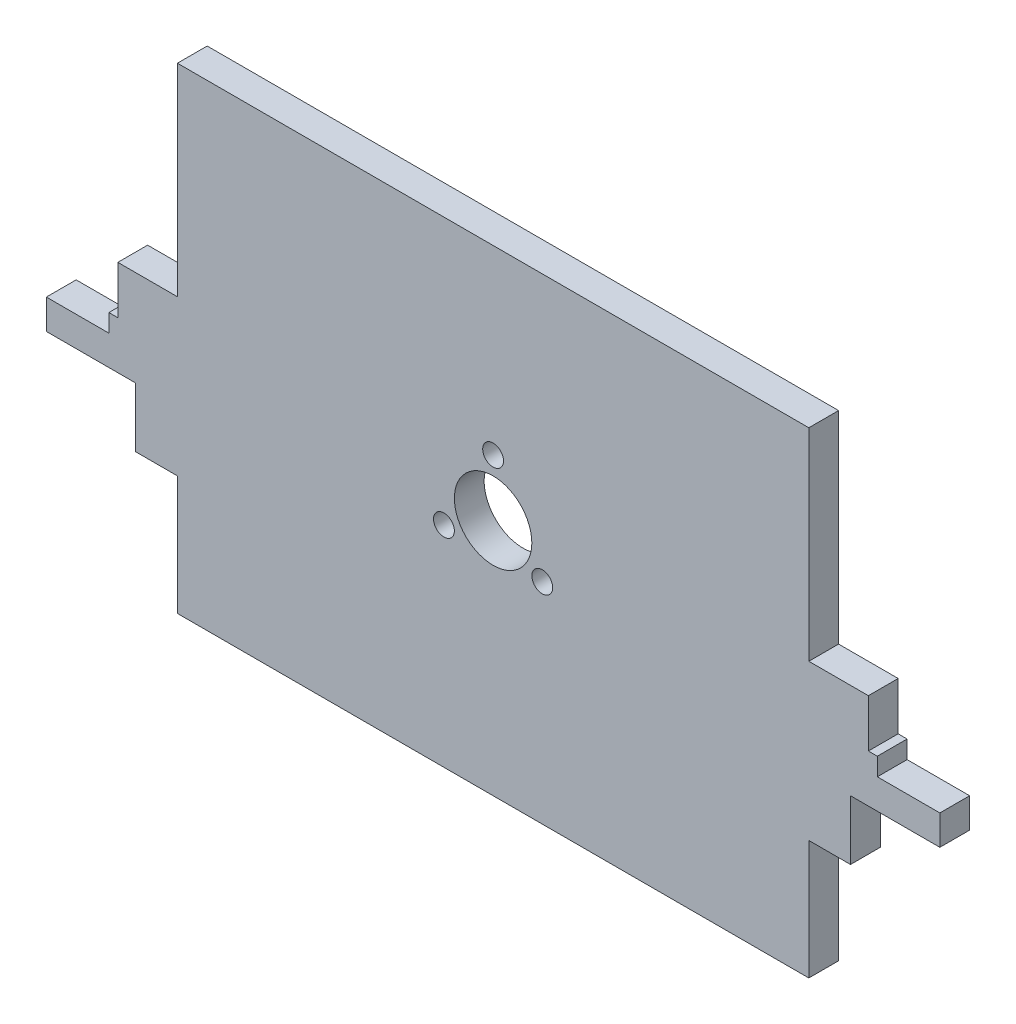
SolidWorks part; units mm, degrees
ref_plane "前视基准面" through (0, 0, 0) normal (0, 0, 1) x (1, 0, 0)
ref_plane "上视基准面" through (0, 0, 0) normal (0, 1, 0) x (1, 0, 0)
ref_plane "右视基准面" through (0, 0, 0) normal (1, 0, 0) x (0, 0, -1)
other "Configuration Table"
sketch "草图1" plane through (0, 0, 0) normal (0, 0, 1) x (1, 0, 0)
  line L1 (60, -45) -> (-60, -45)
  line L2 (60, -45) -> (60, 45)
  line L3 (60, 45) -> (-60, 45)
  line L4 (-60, -45) -> (-60, 45)
  line L5 (60, -45) -> (-60, 45) construction
  line L6 (60, 45) -> (-60, -45) construction
  point P0 (0, 0)
  dimension "D1" = 120
  dimension "D2" = 90
extrude "凸台-拉伸1" add sketch "草图1" along normal blind 5
sketch "草图5" plane through (0, 0, 0) normal (0, 0, -1) x (-1, 0, 0)
  line L0 (60, 45) -> (60, -45) construction
  line L1 (-60, -45) -> (60, -45)
  line L2 (-60, -45) -> (-60, -35)
  line L3 (-60, -35) -> (60, -35)
  line L4 (60, -45) -> (60, -35)
  dimension "D1" = 10
extrude "切除-拉伸3" cut sketch "草图5" against normal blind 10
sketch "草图8" plane through (60, 0, 0) normal (1, 0, 0) x (0, 0, -1)
  line L0 (0, 0.0974) -> (0, -5.0026)
  line L1 (0, -35) -> (0, 45) construction
  line L2 (-50.9779, 0.0974) -> (47.0221, 0.0974) construction
  line L3 (47.0221, -5.0026) -> (-50.9779, -5.0026) construction
  line L4 (0, -5.0026) -> (-5, -5.0026)
  line L5 (-5, -35) -> (-5, 45) construction
  line L6 (-5, -5.0026) -> (-5, 0.0974)
  line L7 (-5, 0.0974) -> (0, 0.0974)
  line L9 (-4.95, -5.0026) -> (-0.05, -5.0026)
  line L10 (-4.95, -5.0026) -> (-4.95, 0.0974)
  line L11 (-4.95, 0.0974) -> (-0.05, 0.0974)
  line L12 (-0.05, -5.0026) -> (-0.05, 0.0974)
  line L13 (-4.95, -5.0026) -> (-0.05, 0.0974) construction
  line L14 (-4.95, 0.0974) -> (-0.05, -5.0026) construction
  point P8 (-2.5, -2.4526)
  dimension "D1" = 0.05
  dimension "D2" = 0.05
  dimension "D3" = 0
  dimension "D4" = 0
sketch "草图10" plane through (60, 0, 0) normal (1, 0, 0) x (0, 0, -1)
  line L0 (-5, -35) -> (-5, 45) construction
  line L1 (0, 0) -> (-5, 0)
  line L2 (-5, 0) -> (-5, -5.0026)
  line L3 (-5, -5.0026) -> (0, -5.0026)
  line L4 (0, -35) -> (0, 45) construction
  line L5 (0, -5.0026) -> (0, 0)
extrude "凸台-拉伸3" add sketch "草图10" along normal blind 15
sketch "草图11" plane through (0, 0, 0) normal (0, 0, -1) x (-1, 0, 0)
  line L0 (0, 45) -> (0, -35) construction
  line L1 (-60, 45) -> (60, 45) construction
  line L2 (60, -35) -> (-60, -35) construction
sketch "草图12" plane through (-60, 0, 0) normal (-1, 0, 0) x (0, 0, 1)
  line L4 (0, 45) -> (0, -35)
  line L5 (0, -35) -> (5, -35)
  line L6 (5, -35) -> (5, 45)
  line L7 (5, 45) -> (0, 45)
  line L8 (0, 45) -> (0, -35)
  line L9 (0, -35) -> (5, -35)
  line L10 (5, -35) -> (5, 45)
  line L11 (5, 45) -> (0, 45)
  line L12 (0, 0) -> (0, -5.0026)
  line L13 (5, 0) -> (0, 0)
  line L14 (5, -5.0026) -> (5, 0)
  line L15 (0, -5.0026) -> (5, -5.0026)
  line L16 (0, 0) -> (0, -5.0026)
  line L17 (5, 0) -> (0, 0)
  line L18 (5, -5.0026) -> (5, 0)
  line L19 (0, -5.0026) -> (5, -5.0026)
  dimension "D1" = 0
  dimension "D2" = 0
extrude "凸台-拉伸4" add sketch "草图12" along normal blind 15 contours L8 L19 L10 L17 region at (-60, -2.5013, 2.5)
sketch "草图13" plane through (0, 0, 5) normal (0, 0, 1) x (1, 0, 0)
  line L0 (-60, 45) -> (60, -35) construction
  line L1 (60, 45) -> (-60, -35) construction
  circle A0 centre (0, 5) radius 6.5
  circle A1 centre (8.2532, 0.235) radius 1.75
  circle A2 centre (-8.2532, 0.235) radius 1.75
  circle A3 centre (0, 5) radius 9.53
  circle A4 centre (0, 14.53) radius 1.75
  point P19 (0, 5)
  dimension "D1" = 13
  dimension "D2" = 19.06
  dimension "D3" = 3.5
  dimension "D4" = 3
extrude "切除-拉伸4" cut sketch "草图13" against normal blind 15 contours A0 | A3 A4 | A3 A4 | A3 A2 | A2 A3 | A3 A1 | A1 A3 region at (0, 5, 5) region at (8.8707, -0.1215, 5) region at (7.5856, 0.6205, 5) region at (-7.5856, 0.6205, 5) region at (-8.8707, -0.1215, 5) region at (0, 13.7591, 5) region at (0, 15.243, 5)
sketch "草图14" plane through (0, 0, 0) normal (0, 0, -1) x (-1, 0, 0)
  line L1 (-60, 0) -> (-63, 0)
  line L2 (-60, 0) -> (-60, 15.4049)
  line L3 (-60, 15.4049) -> (-63, 15.4049)
  line L4 (-63, 0) -> (-63, 15.4049)
  line L5 (60, 0) -> (63, 0)
  line L6 (60, 0) -> (60, 15.4049)
  line L7 (60, 15.4049) -> (63, 15.4049)
  line L8 (63, 0) -> (63, 15.4049)
  dimension "D1" = 3
  dimension "D2" = 3
extrude "凸台-拉伸5" add sketch "草图14" against normal through all
sketch "草图15" plane through (0, 0, 0) normal (0, 0, -1) x (-1, 0, 0)
  line L0 (57.8483, 15.0474) -> (42.4709, 15.0474)
  line L1 (35, 15.0474) -> (64, 15.0474) construction
  line L2 (54.2916, -16.9526) -> (42.4709, -16.9526)
  line L3 (35, -16.9526) -> (65, -16.9526) construction
sketch "草图16" plane through (0, 0, 0) normal (0, 0, -1) x (-1, 0, 0)
  line L0 (63, 0) -> (63, 15.4049) construction
  line L1 (63, 15.0474) -> (58, 15.0474)
  line L2 (63, 15.0474) -> (63, 45)
  line L3 (63, 45) -> (58, 45)
  line L4 (58, 15.0474) -> (58, 45)
  line L5 (-60, 45) -> (60, 45) construction
  line L6 (0, 45) -> (0, 34.2165)
  line L7 (0, 45) -> (0, -35) construction
  line L8 (-63, 45) -> (-58, 45)
  line L9 (-58, 15.0474) -> (-58, 45)
  line L10 (-63, 15.0474) -> (-58, 15.0474)
  line L11 (-63, 15.0474) -> (-63, 45)
  line M6 (-60, 45) -> (-60, 15.4049)
  line M7 (-60, 15.4049) -> (-63, 15.4049)
  line M18 (63, 0) -> (63, 15.4049)
  line M19 (63, 15.4049) -> (60, 15.4049)
  line M20 (60, 15.4049) -> (60, 45)
  line M21 (60, 45) -> (-60, 45)
  dimension "D1" = 5
extrude "切除-拉伸5" cut sketch "草图16" against normal blind 10 contours L11 L8 M7 M6 | L4 L1 M18 M19 M20 M21 | L9 L8 L11 L10 region at (-59.044, 29.7634, 0) region at (61.5, 30.2025, 0)
sketch "草图17" plane through (0, 0, 0) normal (0, 0, -1) x (-1, 0, 0)
  line L0 (-58, 45) -> (58, 45) construction
  line L1 (-58, 15.0474) -> (-53, 15.0474)
  line L2 (-58, 15.0474) -> (-58, 45)
  line L3 (-58, 45) -> (-53, 45)
  line L4 (-53, 15.0474) -> (-53, 45)
  line L6 (58, 15.0474) -> (53, 15.0474)
  line L7 (58, 15.0474) -> (58, 45)
  line L8 (58, 45) -> (53, 45)
  line L9 (53, 15.0474) -> (53, 45)
  dimension "D1" = 5
  dimension "D2" = 5
extrude "切除-拉伸6" cut sketch "草图17" against normal blind 10
sketch "草图18" plane through (0, 0, 0) normal (0, 0, -1) x (-1, 0, 0)
  line L1 (-63, 15.0474) -> (-53, 15.0474)
  line L2 (-63, 15.0474) -> (-63, 11.0474)
  line L3 (-63, 11.0474) -> (-53, 11.0474)
  line L4 (-53, 15.0474) -> (-53, 11.0474)
  line L9 (0, 31.9614) -> (0, 24.6178)
  line L10 (60, -35) -> (53, -35)
  line L11 (60, -35) -> (60, -15)
  line L12 (60, -15) -> (53, -15)
  line L13 (53, -35) -> (53, -15)
  line L14 (0, 45) -> (0, -35) construction
  line L15 (-60, -15) -> (-53, -15)
  line L16 (-53, -35) -> (-53, -15)
  line L17 (-60, -35) -> (-53, -35)
  line L18 (-60, -35) -> (-60, -15)
  line L19 (63, 11.0474) -> (53, 11.0474)
  line L20 (53, 15.0474) -> (53, 11.0474)
  line L21 (63, 15.0474) -> (53, 15.0474)
  line L22 (63, 15.0474) -> (63, 11.0474)
  line M16 (-53, 15.0474) -> (-63, 15.0474)
  line M17 (-63, 15.0474) -> (-63, 0)
  line M21 (-60, -5.0026) -> (-60, -35)
  line M22 (-60, -35) -> (60, -35)
  line M23 (60, -35) -> (60, -5.0026)
  line M27 (63, 0) -> (63, 15.0474)
  line M28 (63, 15.0474) -> (53, 15.0474)
  dimension "D1" = 20
  dimension "D2" = 4
extrude "切除-拉伸7" cut sketch "草图18" against normal blind 10 contours L4 L3 M16 M17 | L16 L15 M22 M21 | L13 L12 M22 M23 | L20 L19 M28 M27 region at (58, 13.0474, 0) region at (56.5, -25, 0) region at (-56.5, -25, 0) region at (-58, 13.0474, 0)
sketch "草图19" plane through (0, 0, 0) normal (0, 0, -1) x (-1, 0, 0)
  line L0 (0, 45) -> (0, 37.9412)
  line L1 (-63, 0) -> (-64.5, 0)
  line L2 (-63, 0) -> (-63, 3)
  line L3 (-63, 3) -> (-64.5, 3)
  line L4 (-64.5, 0) -> (-64.5, 3)
  line L5 (0, 45) -> (0, -35) construction
  line L6 (63, 3) -> (64.5, 3)
  line L7 (64.5, 0) -> (64.5, 3)
  line L8 (63, 0) -> (64.5, 0)
  line L9 (63, 0) -> (63, 3)
  line M15 (-63, 11.0474) -> (-63, 0)
  line M16 (-63, 0) -> (-75, 0)
  dimension "D1" = 1.5
  dimension "D2" = 3
extrude "凸台-拉伸6" add sketch "草图19" against normal through all contours L4 L3 M16 M15 | L9 L6 L7 L8 region at (63.75, 1.5, 0)
